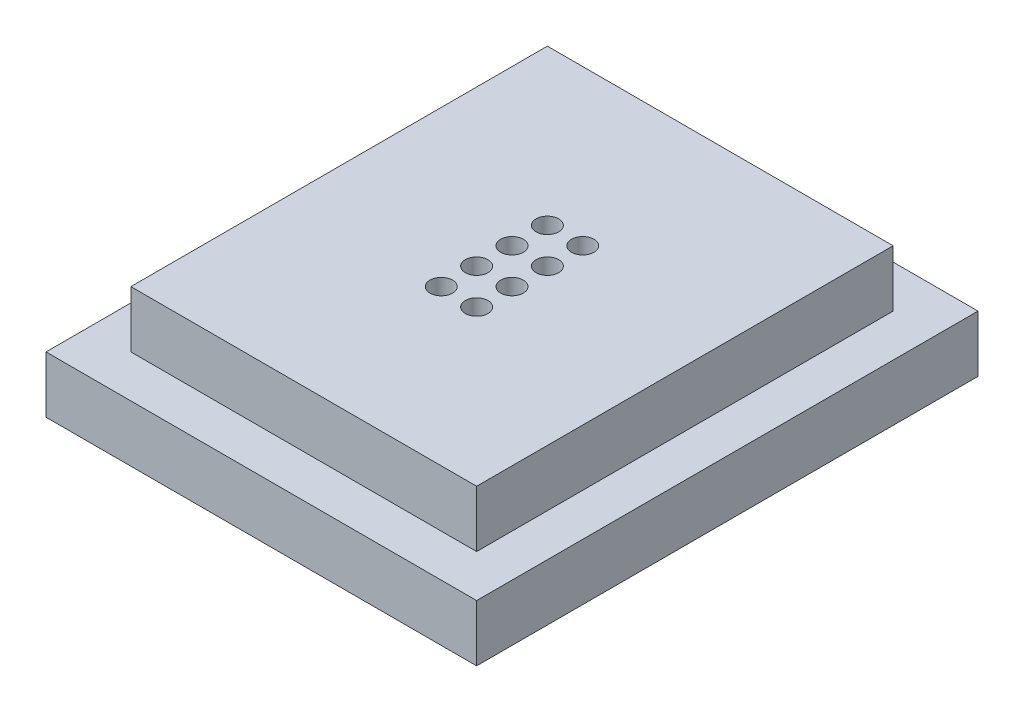
SolidWorks part; units mm, degrees
note: The reader was unsure of these and kept them because the rebuilt part matched: shared geometry of "Croquis1<20>", "Croquis1<21>".
other "Marca1"
sketch "Croquis2" plane through (-8.97, 3, 10.42) normal (-0.2345, 0.7487, 0.62) x (0.9671, 0.1154, 0.2265)
material "ABS"
ref_plane "Alzado" through (0, 0, 0) normal (0, 0, 1) x (1, 0, 0)
ref_plane "Planta" through (0, 0, 0) normal (0, 1, 0) x (1, 0, 0)
ref_plane "Vista lateral" through (0, 0, 0) normal (1, 0, 0) x (0, 0, -1)
sketch "Croquis1" plane through (0, 0, 0) normal (0, 1, 0) x (1, 0, 0)
  line L6 (3.95, 2.55) -> (8.05, 2.55) construction
  line L7 (3.95, 2.55) -> (3.95, 11.6524) construction
  line L8 (3.95, 11.6524) -> (8.05, 11.6524) construction
  line L9 (8.05, 2.55) -> (8.05, 11.6524) construction
  line L13 (16.225, -5.625) -> (-4.225, -5.625)
  line L14 (-4.225, -5.625) -> (-4.225, 19.8274)
  line L15 (16.225, 19.8274) -> (-4.225, 19.8274)
  line L16 (16.225, -5.625) -> (16.225, 19.8274)
  line L17 (10.55, 0.05) -> (1.45, 0.05)
  line L18 (10.55, 0.05) -> (10.55, 14.1524)
  line L19 (10.55, 14.1524) -> (1.45, 14.1524)
  line L20 (1.45, 0.05) -> (1.45, 14.1524)
  line L21 (-9.225, -10.625) -> (-9.225, 24.8274)
  line L22 (21.225, 24.8274) -> (-9.225, 24.8274)
  line L23 (21.225, -10.625) -> (21.225, 24.8274)
  line L24 (21.225, -10.625) -> (-9.225, -10.625)
  line L25 (10.55, 7.1012) -> (1.45, 7.1012) construction
  line L26 (6, 0.05) -> (6, 14.1524) construction
  line L27 (18.225, -7.625) -> (-6.225, -7.625)
  line L28 (6, 24.8274) -> (6, -10.625) construction
  line L29 (-6.225, -7.625) -> (-6.225, 21.8274)
  line L30 (18.225, 21.8274) -> (-6.225, 21.8274)
  line L31 (18.225, -7.625) -> (18.225, 21.8274)
  circle A0 centre (7.25, 3.35) radius 0.8
  circle A1 centre (4.75, 3.35) radius 0.8
  circle A2 centre (4.75, 5.8508) radius 0.8
  circle A3 centre (4.75, 8.3516) radius 0.8
  circle A4 centre (4.75, 10.8524) radius 0.8
  circle A5 centre (7.25, 5.8508) radius 0.8
  circle A6 centre (7.25, 8.3516) radius 0.8
  circle A7 centre (7.25, 10.8524) radius 0.8
  circle A8 centre (7.25, 3.35) radius 1.1
  circle A9 centre (4.75, 3.35) radius 1.1
  circle A10 centre (4.75, 5.8508) radius 1.1
  circle A11 centre (7.25, 5.8508) radius 1.1
  circle A12 centre (7.25, 8.3516) radius 1.1
  circle A13 centre (4.75, 8.3516) radius 1.1
  circle A14 centre (4.75, 10.8524) radius 1.1
  circle A15 centre (7.25, 10.8524) radius 1.1
  point P1 (6, 7.1012)
  point P39 (10.55, 7.1012)
  point P45 (6, 2.55)
  point P49 (6, 11.6524)
  dimension "D1" = 2
  dimension "D6" = 1.6
  dimension "D7" = 2.5
  dimension "D16" = 2.5008
  dimension "D22" = 5.675
  dimension "D8" = 2.5008
  dimension "D9" = 2.5008
  dimension "D27" = 2.2
  dimension "D4" = 2.5
  dimension "D5" = 2.5
  dimension "D10" = 4.1
  dimension "D11" = 9.1
  dimension "D12" = 5
  dimension "D14" = 5
  dimension "D15" = 5
  dimension "D17" = 5
  dimension "D18" = 2.5008
  dimension "D19" = 2.5
  dimension "D20" = 5.675
  dimension "D21" = 5.675
  dimension "D23" = 20.45
  dimension "D24" = 25.4524
  dimension "D13" = 15.225
  dimension "D25" = 30.45
  dimension "D26" = 35.4524
  dimension "D28" = 2.5008
  dimension "D29" = 2.5008
  dimension "D31" = 2.5
  dimension "D32" = 14.1024
  dimension "D33" = 5.675
  dimension "D30" = 2
  dimension "D2" = 4
extrude "Saliente-Extruir4" add sketch "Croquis1" along normal blind 4 contours A9 A1 | A8 A0 | A11 A5 | A10 A2 | A13 A3 | A14 A4 | A15 A7 | A12 A6 | L20 L17 L18 L19 A15 A14 A13 A12 A11 A10 A9 A8 | L13 L16 L15 L14 L17 L20 L19 L18 | L27 L31 L30 L29 L16 L13 L14 L15
extrude "Cortar-Extruir1" cut sketch "Croquis1<20>" along normal blind 2.3 contours A8 A0 | A11 A5 | A9 A1 | A10 A2 | A13 A3 | A14 A4 | A15 A7 | A12 A6
sketch "Croquis1<20>" plane through (0, 0, 0) normal (0, 1, 0) x (1, 0, 0) same geometry as "Croquis1"
extrude "Saliente-Extruir7" add sketch "Croquis1<21>" against normal blind 4 contours L13 L16 L15 L14 L17 L20 L19 L18 | L20 L17 L18 L19 A15 A14 A13 A12 A11 A10 A9 A8 | L21 L22 L23 L24
sketch "Croquis1<21>" plane through (0, 0, 0) normal (0, 1, 0) x (1, 0, 0) same geometry as "Croquis1"
ref_plane "Plano1" through (0, -3, 0) normal (0, -1, 0) x (-1, 0, 0)
sketch "Croquis3" plane through (0, -3, 0) normal (0, -1, 0) x (-1, 0, 0)
  line L0 (-16.225, 7.1012) -> (-16.725, 7.1012) construction
  line L1 (-16.225, -6.125) -> (4.225, -6.125)
  line L2 (-16.225, -6.125) -> (-16.225, -5.625)
  line L3 (-16.225, -5.625) -> (4.225, -5.625)
  line L4 (4.225, -6.125) -> (4.225, -5.625)
  line L5 (-16.225, -6.125) -> (4.225, -5.625) construction
  line L6 (-16.225, -5.625) -> (4.225, -6.125) construction
  line L7 (4.225, -5.625) -> (4.725, -5.625)
  line L8 (4.225, -5.625) -> (4.225, 19.8274)
  line L9 (4.225, 19.8274) -> (4.725, 19.8274)
  line L10 (4.725, -5.625) -> (4.725, 19.8274)
  line L11 (4.225, 19.8274) -> (-16.225, 19.8274)
  line L12 (4.225, 19.8274) -> (4.225, 20.3274)
  line L13 (4.225, 20.3274) -> (-16.225, 20.3274)
  line L14 (-16.225, 19.8274) -> (-16.225, 20.3274)
  line L15 (-16.225, 19.8274) -> (-16.725, 19.8274)
  line L16 (-16.225, 19.8274) -> (-16.225, -5.625)
  line L17 (-16.225, -5.625) -> (-16.725, -5.625)
  line L18 (-16.725, 19.8274) -> (-16.725, -5.625)
  line L19 (-6, -6.125) -> (-6, -5.625) construction
  line L20 (-16.225, 11.6012) -> (-16.725, 11.6012)
  line L21 (-16.225, 11.6012) -> (-16.225, 2.6012)
  line L22 (-16.225, 2.6012) -> (-16.725, 2.6012)
  line L23 (-16.725, 11.6012) -> (-16.725, 2.6012)
  line L24 (-16.225, 11.6012) -> (-16.725, 2.6012) construction
  line L25 (-16.225, 2.6012) -> (-16.725, 11.6012) construction
  line L26 (4.725, 7.1012) -> (4.225, 7.1012) construction
  line L27 (-10.4984, -5.625) -> (-1.5016, -5.625)
  line L28 (-10.4984, -5.625) -> (-10.4984, -6.125)
  line L29 (-10.4984, -6.125) -> (-1.5016, -6.125)
  line L30 (-1.5016, -5.625) -> (-1.5016, -6.125)
  line L31 (-10.4984, -5.625) -> (-1.5016, -6.125) construction
  line L32 (-10.4984, -6.125) -> (-1.5016, -5.625) construction
  line L33 (-6, 20.3274) -> (-6, 19.8274) construction
  line L34 (4.225, 11.6012) -> (4.725, 11.6012)
  line L35 (4.225, 11.6012) -> (4.225, 2.6012)
  line L36 (4.225, 2.6012) -> (4.725, 2.6012)
  line L37 (4.725, 11.6012) -> (4.725, 2.6012)
  line L38 (4.225, 11.6012) -> (4.725, 2.6012) construction
  line L39 (4.225, 2.6012) -> (4.725, 11.6012) construction
  line L41 (-10.5, 20.3274) -> (-1.5, 20.3274)
  line L42 (-10.5, 20.3274) -> (-10.5, 19.8274)
  line L43 (-10.5, 19.8274) -> (-1.5, 19.8274)
  line L44 (-1.5, 20.3274) -> (-1.5, 19.8274)
  line L45 (-10.5, 20.3274) -> (-1.5, 19.8274) construction
  line L46 (-10.5, 19.8274) -> (-1.5, 20.3274) construction
  point P0 (-6, -5.875)
  point P15 (-16.475, 7.1012)
  point P22 (-6, -5.875)
  point P30 (4.475, 7.1012)
  point P36 (4.475, 2.6012)
  point P41 (-6, 20.0774)
  dimension "D1" = 0.5
  dimension "D2" = 0.5
  dimension "D3" = 0.5
  dimension "D4" = 0.5
  dimension "D5" = 9
  dimension "D6" = 9
  dimension "D7" = 9
extrude "Cortar-Extruir2" cut sketch "Croquis3" against normal blind 0.7 contours L15 L18 L17 L16 | L1 L4 L3 L2 | L7 L10 L9 L8 | L14 L11 L12 L13
fillet "Redondeo1" radius 0.2 2 edges at (16.225, -2.3, -7.1012) (16.225, -3, -7.1012)
fillet "Redondeo2" radius 0.2 2 edges at (-4.225, -3, -7.1012) (-4.225, -2.3, -7.1012)
fillet "Redondeo3" radius 0.2 2 edges at (6, -2.3, 5.625) (6, -3, 5.625)
fillet "Redondeo4" radius 0.2 2 edges at (6, -3, -19.8274) (6, -2.3, -19.8274)
sketch "Croquis5" plane through (0, -4, 0) normal (0, -1, 0) x (1, 0, 0)
  line L14 (-7.725, -23.3274) -> (19.725, -23.3274)
  line L15 (19.725, -23.3274) -> (19.725, 9.125)
  line L16 (19.725, 9.125) -> (-7.725, 9.125)
  line L17 (-7.725, 9.125) -> (-7.725, -23.3274)
  line L18 (-5.225, -20.8274) -> (17.225, -20.8274)
  line L19 (17.225, -20.8274) -> (17.225, 6.625)
  line L20 (17.225, 6.625) -> (-5.225, 6.625)
  line L21 (-5.225, 6.625) -> (-5.225, -20.8274)
  line L22 (-5.225, -20.8274) -> (17.225, -20.8274)
  line L23 (17.225, -20.8274) -> (17.225, 6.625)
  line L24 (17.225, 6.625) -> (-5.225, 6.625)
  line L25 (-5.225, 6.625) -> (-5.225, -20.8274)
  dimension "D1" = 1
  dimension "D2" = 2.5
extrude "Cortar-Extruir4" cut sketch "Croquis5" against normal blind 2
sketch "Croquis6" plane through (0, 0, -23.3274) normal (0, 0, 1) x (1, 0, 0)
  line L0 (6, -2) -> (6, -4) construction
  line L1 (-7.725, -2) -> (19.725, -2) construction
  line L2 (-7.725, -4) -> (19.725, -4) construction
  line L4 (1.5, -2.75) -> (10.5, -2.75)
  line L5 (1.5, -2.75) -> (1.5, -3.25)
  line L6 (1.5, -3.25) -> (10.5, -3.25)
  line L7 (10.5, -2.75) -> (10.5, -3.25)
  line L8 (1.5, -2.75) -> (10.5, -3.25) construction
  line L9 (1.5, -3.25) -> (10.5, -2.75) construction
  point P6 (6, -3)
  dimension "D1" = 0.5
  dimension "D2" = 9
extrude "Cortar-Extruir5" cut sketch "Croquis6" against normal blind 0.5
sketch "Croquis7" plane through (0, 0, 9.125) normal (0, 0, -1) x (-1, 0, 0)
  line L0 (-6, -2) -> (-6, -4) construction
  line L1 (-19.725, -2) -> (7.725, -2) construction
  line L2 (-19.725, -4) -> (7.725, -4) construction
  line L4 (-1.5, -2.75) -> (-10.5, -2.75)
  line L5 (-1.5, -2.75) -> (-1.5, -3.25)
  line L6 (-1.5, -3.25) -> (-10.5, -3.25)
  line L7 (-10.5, -2.75) -> (-10.5, -3.25)
  line L8 (-1.5, -2.75) -> (-10.5, -3.25) construction
  line L9 (-1.5, -3.25) -> (-10.5, -2.75) construction
  point P6 (-6, -3)
  dimension "D1" = 0.5
  dimension "D2" = 9
extrude "Cortar-Extruir6" cut sketch "Croquis7" against normal blind 0.5
sketch "Croquis8" plane through (0, 0, 0) normal (0, -1, 0) x (1, 0, 0)
  line L0 (6, -2.25) -> (6, -11.9524)
  line L1 (8.35, -11.9524) -> (3.65, -11.9524)
  line L2 (8.35, -11.9524) -> (8.35, -2.25)
  line L3 (8.35, -2.25) -> (3.65, -2.25)
  line L4 (3.65, -11.9524) -> (3.65, -2.25)
  line L5 (8.35, -7.1012) -> (3.65, -7.1012)
  line L6 (8.35, -7.1012) -> (8.35, -2.25) construction
  line L7 (3.65, -7.1012) -> (3.65, -11.9524) construction
  line L8 (8.35, -2.25) -> (8.35, -7.1012) construction
  line L9 (8.35, -7.1012) -> (8.35, -4.6756) construction
  line L10 (8.35, -4.6756) -> (3.65, -4.6756) construction
  line L11 (3.65, -11.9524) -> (3.65, -7.1012) construction
  line L12 (3.65, -7.1012) -> (3.65, -9.5268) construction
  line L13 (3.65, -9.5268) -> (8.35, -9.5268) construction
  line L14 (2.65, -12.9524) -> (2.65, -1.25)
  line L15 (8.35, -9.5268) -> (3.65, -9.5268)
  line L16 (8.35, -9.5268) -> (8.35, -11.9524)
  line L17 (8.35, -11.9524) -> (3.65, -11.9524)
  line L18 (3.65, -9.5268) -> (3.65, -11.9524)
  line L19 (8.35, -7.1012) -> (3.65, -7.1012)
  line L20 (8.35, -7.1012) -> (8.35, -9.5268)
  line L21 (8.35, -9.5268) -> (3.65, -9.5268)
  line L22 (3.65, -7.1012) -> (3.65, -9.5268)
  line L23 (8.35, -4.6756) -> (3.65, -4.6756)
  line L24 (8.35, -4.6756) -> (8.35, -7.1012)
  line L25 (8.35, -7.1012) -> (3.65, -7.1012)
  line L26 (3.65, -4.6756) -> (3.65, -7.1012)
  line L27 (8.35, -2.25) -> (3.65, -2.25)
  line L28 (8.35, -2.25) -> (8.35, -4.6756)
  line L29 (8.35, -4.6756) -> (3.65, -4.6756)
  line L30 (3.65, -2.25) -> (3.65, -4.6756)
  line L31 (9.35, -1.25) -> (2.65, -1.25)
  line L32 (9.35, -12.9524) -> (9.35, -1.25)
  line L33 (9.35, -12.9524) -> (2.65, -12.9524)
  circle A0 centre (7.25, -3.35) radius 1.1 construction
  circle A1 centre (4.75, -3.35) radius 1.1 construction
  circle A2 centre (7.25, -10.8524) radius 1.1 construction
  circle A5 centre (4.75, -8.3516) radius 1.1
  circle A6 centre (4.75, -8.3516) radius 1.1
  circle A8 centre (7.25, -5.8508) radius 1.1
  circle A9 centre (7.25, -5.8508) radius 1.1
  circle A11 centre (4.75, -5.8508) radius 1.1
  circle A12 centre (4.75, -5.8508) radius 1.1
  circle A14 centre (7.25, -10.8524) radius 1.1
  circle A15 centre (7.25, -10.8524) radius 1.1
  circle A16 centre (7.25, -3.35) radius 1.1
  circle A17 centre (4.75, -10.8524) radius 1.1
  circle A18 centre (4.75, -10.8524) radius 1.1
  circle A19 centre (7.25, -3.35) radius 1.1
  circle A20 centre (7.25, -8.3516) radius 1.1
  circle A21 centre (7.25, -8.3516) radius 1.1
  circle A23 centre (4.75, -3.35) radius 1.1
  circle A24 centre (4.75, -3.35) radius 1.1
  circle M13 centre (7.25, -3.35) radius 1.1
  circle M14 centre (7.25, -8.3516) radius 1.1
  circle M15 centre (7.25, -10.8524) radius 1.1
  circle M16 centre (4.75, -10.8524) radius 1.1
  circle M17 centre (7.25, -5.8508) radius 1.1
  circle M18 centre (4.75, -3.35) radius 1.1
  circle M19 centre (4.75, -5.8508) radius 1.1
  circle M20 centre (4.75, -8.3516) radius 1.1
  dimension "D1" = 0
  dimension "D2" = 0
  dimension "D3" = 0
  dimension "D4" = 0
  dimension "D5" = 0
  dimension "D6" = 0
  dimension "D7" = 0
  dimension "D8" = 0
  dimension "D9" = 1
extrude "Saliente-Extruir14" add sketch "Croquis8" along normal blind 1 contours L33 L32 L31 L14 L1 L4 L3 L2 | L1 L2 M15 | L2 L15 L0 L1 M15 | L0 L15 L4 L1 M16 | L4 L1 M16 | L15 L0 L5 L4 M20 | L15 L2 L5 L0 M14 | L2 L23 L0 L5 M17 | L0 L23 L4 L5 M19 | L23 L2 L3 L0 M13 | L2 L3 M13 | L23 L0 L3 L4 M18 | L4 L3 M18
fillet "Redondeo6" radius 0.1 8 edges at (7.25, -1, -4.45) (4.75, -1, -4.45) (7.25, -1, -6.9508) (4.75, -1, -6.9508) (7.25, -1, -9.4516) (4.75, -1, -9.4516) (4.75, -1, -11.9524) (7.25, -1, -11.9524)
fillet "Redondeo7" radius 0.5 4 edges at (2.65, -1, -7.1012) (6, -1, -1.25) (6, -1, -12.9524) (9.35, -1, -7.1012)
